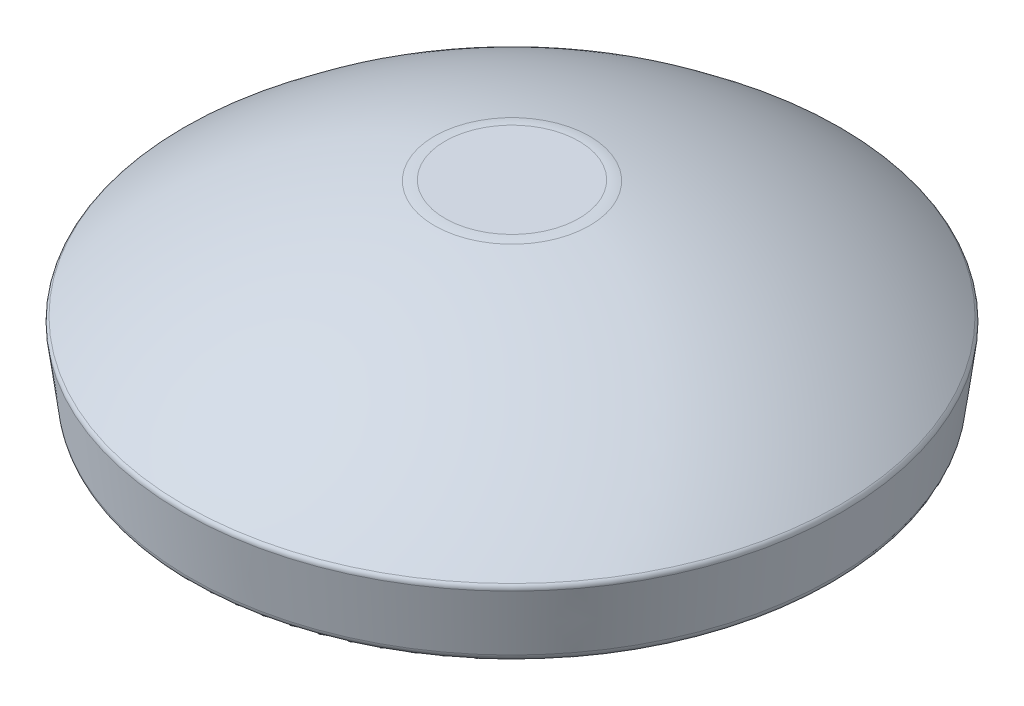
SolidWorks part; units mm, degrees
material "6061-T6 (SS)"
ref_plane "Front Plane" through (0, 0, 0) normal (0, 0, 1) x (1, 0, 0)
ref_plane "Top Plane" through (0, 0, 0) normal (0, 1, 0) x (1, 0, 0)
ref_plane "Right Plane" through (0, 0, 0) normal (1, 0, 0) x (0, 0, -1)
sketch "Sketch2" plane through (0, 0, 0) normal (0, 0, 1) x (1, 0, 0)
  line L0 (0, 0) -> (14.097, 0)
  line L1 (14.097, 0) -> (14.515, 3.175)
  line L4 (0, 0) -> (0, 14.8028) construction
  line L7 (3.175, 8.4629) -> (-12.1682, 11.1683) construction
  line L8 (14.515, 3.175) -> (20.479, -1.8294) construction
  line L10 (0, 8.4629) -> (3.175, 8.4629)
  line L11 (0, 8.4629) -> (0, 0)
  arc A0 (14.515, 3.175) -> (3.175, 8.4629) centre (-1.0224, -15.3418) ccw
  dimension "D5" = 40
  dimension "D1" = 3.175
  dimension "D2" = 28.194
  dimension "D3" = 7.5
  dimension "D4" = 29.03
  dimension "D6" = 80
  dimension "D7" = 6.35
revolve "Revolve1" add sketch "Sketch2" angle 360 about L4
sketch "Sketch3" plane through (0, 0, 0) normal (0, -1, 0) x (1, 0, 0)
  line L0 (0, -0.7937) -> (0, 0.7937) construction
  line L1 (-3.0742, 0.7937) -> (3.0742, 0.7937)
  line L3 (-3.0742, -0.7937) -> (3.0742, -0.7937)
  arc A0 (-3.0742, -0.7937) -> (3.0742, -0.7937) centre (0, 0) ccw
  arc A1 (3.0742, 0.7937) -> (-3.0742, 0.7937) centre (0, 0) ccw
  point P10 (0, 0)
  dimension "D1" = 6.35
  dimension "D2" = 1.5875
extrude "Boss-Extrude1" add sketch "Sketch3" along normal blind 2.54
fillet "Bottom/Top Rounds" radius 2.54 3 edges at (0, 0, -3.175) (0, 0, 3.175) (3.175, 8.4629, 0)
fillet "Side Round" radius 0.254 1 edges at (14.515, 3.175, 0)
fillet "Match Tool Radius" radius 0.4064 1 edges at (14.097, 0, 0)
